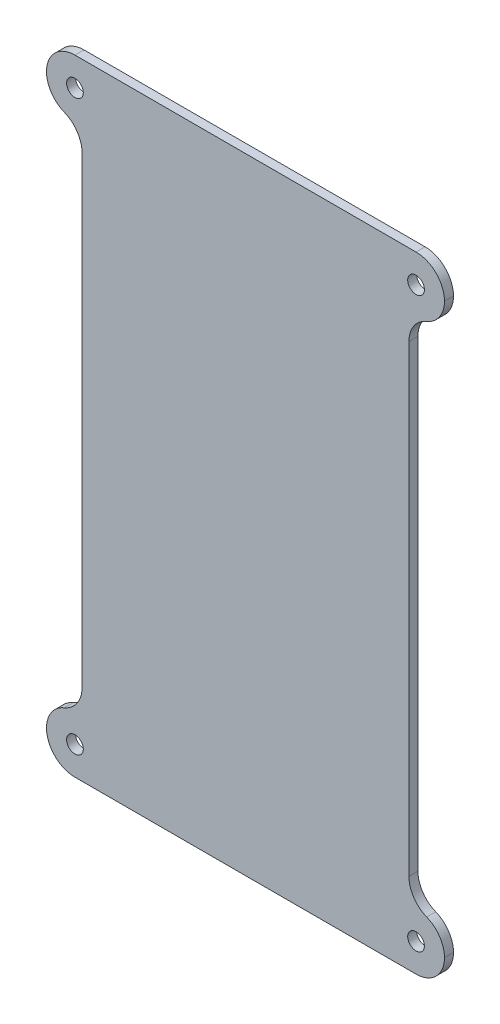
SolidWorks part; units mm, degrees
material "5052-H36"
ref_plane "Front Plane" through (0, 0, 0) normal (0, 0, 1) x (1, 0, 0)
ref_plane "Top Plane" through (0, 0, 0) normal (0, 1, 0) x (1, 0, 0)
ref_plane "Right Plane" through (0, 0, 0) normal (1, 0, 0) x (0, 0, -1)
sketch "Sketch1" plane through (0, 0, 0) normal (0, 0, 1) x (1, 0, 0)
  line L1 (-56, -88) -> (56, -88)
  line L2 (-56, -88) -> (-56, 88)
  line L3 (-56, 88) -> (56, 88)
  line L4 (56, -88) -> (56, 88)
  line L5 (-56, -88) -> (56, 88) construction
  line L6 (-56, 88) -> (56, -88) construction
  circle A0 centre (-48, 80) radius 2.35
  circle A1 centre (48, 80) radius 2.35
  circle A2 centre (48, -80) radius 2.35
  circle A3 centre (-48, -80) radius 2.35
  point P0 (0, 0)
  point P14 (0, 0)
  point P15 (0, 0)
  point P16 (0, 0)
  point P17 (24.5896, -30.4388)
  point P18 (0, 0)
  point P19 (0, 0)
  point P20 (75.4846, 141.2807)
  point P21 (0, 0)
  point P22 (0, 0)
  point P23 (0, 0)
  point P24 (0, 0)
  dimension "D1" = 4.7
  dimension "D2" = 160
  dimension "D3" = 96
  dimension "D4" = 8
  dimension "D5" = 8
  dimension "D6" = 8
  dimension "D7" = 8
extrude "Boss-Extrude1" add sketch "Sketch1" along normal blind 2.54
fillet "Fillet1" radius 8 4 edges at (-56, -88, 1.27) (56, -88, 1.27) (56, 88, 1.27) (-56, 88, 1.27)
sketch "Sketch2" plane through (0, 0, 2.54) normal (0, 0, 1) x (1, 0, 0)
  line L0 (-56, 72) -> (-46, 72)
  line L1 (-56, 80) -> (-56, -80) construction
  line L2 (-46, 72) -> (-46, -72)
  line L3 (-46, -72) -> (-56, -72)
  line L4 (48, 88) -> (-48, 88) construction
  line L5 (-48, -88) -> (48, -88) construction
  line L6 (-56, 72) -> (-56, -72)
  line L7 (56, 72) -> (46, 72)
  line L8 (56, -80) -> (56, 80) construction
  line L9 (46, 72) -> (46, -72)
  line L10 (46, -72) -> (56, -72)
  line L11 (56, -72) -> (56, 72)
  point P15 (56, 72)
  dimension "D1" = 16
  dimension "D2" = 16
  dimension "D3" = 10
  dimension "D4" = 16
  dimension "D5" = 10
  dimension "D6" = 16
extrude "Cut-Extrude1" cut sketch "Sketch2" against normal blind 3.18
fillet "Fillet2" radius 8 4 edges at (56, 72, 1.27) (56, -72, 1.27) (-56, -72, 1.27) (-56, 72, 1.27)
fillet "Fillet3" radius 8 4 edges at (46, -72, 1.27) (46, 72, 1.27) (-46, 72, 1.27) (-46, -72, 1.27)
